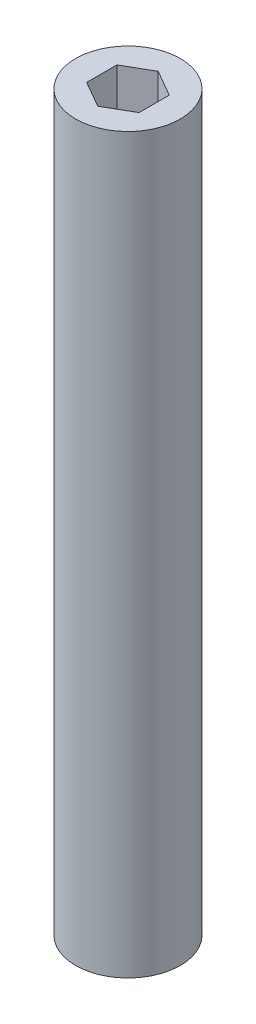
SolidWorks part; units mm, degrees
ref_plane "Front Plane" through (0, 0, 0) normal (0, 0, 1) x (1, 0, 0)
ref_plane "Top Plane" through (0, 0, 0) normal (0, 1, 0) x (1, 0, 0)
ref_plane "Right Plane" through (0, 0, 0) normal (1, 0, 0) x (0, 0, -1)
sketch "Sketch1" plane through (0, 0, 0) normal (0, 1, 0) x (1, 0, 0)
  circle A0 centre (0, 0) radius 12.7
  dimension "D1" = 25.4
extrude "Boss-Extrude1" add sketch "Sketch1" along normal blind 177.8
sketch "Sketch2" plane through (0, 177.8, 0) normal (0, 1, 0) x (1, 0, 0)
  line L1 (0, 7.3323) -> (-6.35, 3.6662)
  line L2 (-6.35, 3.6662) -> (-6.35, -3.6662)
  line L3 (-6.35, -3.6662) -> (0, -7.3323)
  line L4 (0, -7.3323) -> (6.35, -3.6662)
  line L5 (6.35, -3.6662) -> (6.35, 3.6662)
  line L6 (6.35, 3.6662) -> (0, 7.3323)
  circle A0 centre (0, 0) radius 6.35 construction
  dimension "D1" = 12.7
extrude "Cut-Extrude1" cut sketch "Sketch2" against normal up to surface (177.8 mm away) up to face at (0, 0, 12.7)
